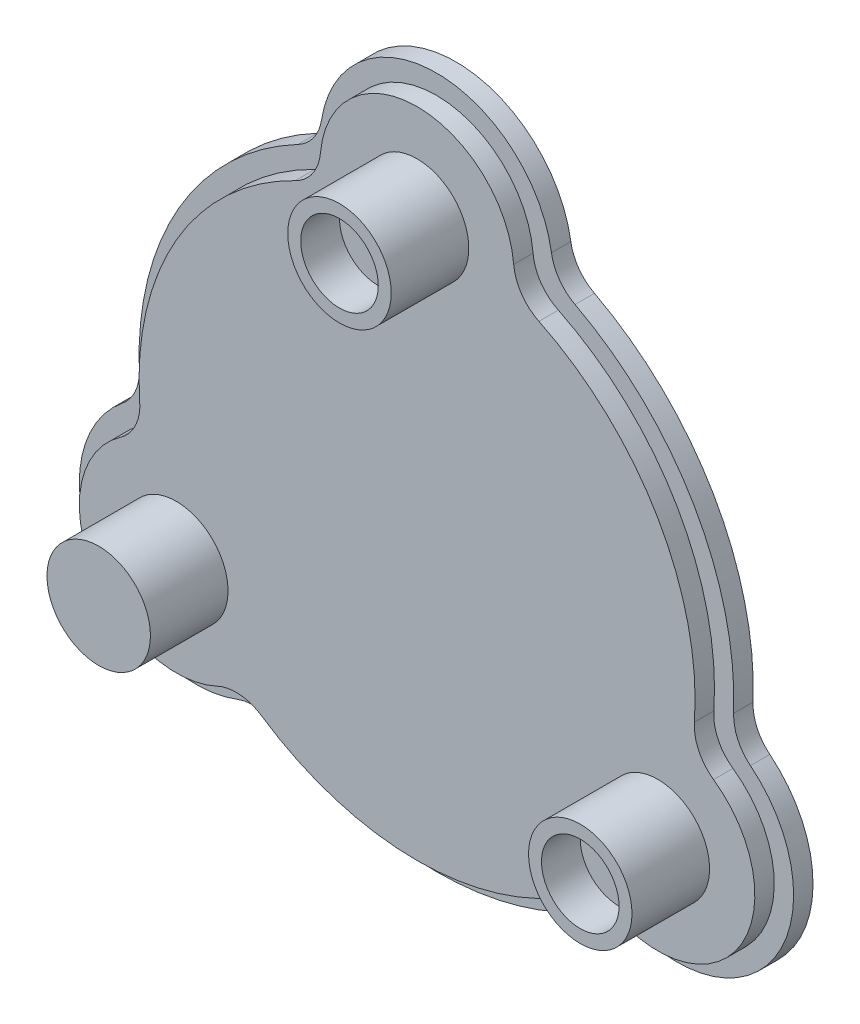
SolidWorks part; units mm, degrees
material "PE Low/Medium Density"
ref_plane "Front Plane" through (0, 0, 0) normal (0, 0, 1) x (1, 0, 0)
ref_plane "Top Plane" through (0, 0, 0) normal (0, 1, 0) x (1, 0, 0)
ref_plane "Right Plane" through (0, 0, 0) normal (1, 0, 0) x (0, 0, -1)
sketch "Sketch1" plane through (0, 0, 0) normal (0, 0, 1) x (1, 0, 0)
  arc A0 (-18846.1535, 38650) -> (-42894.9586, -3003.7523) centre (0, 0) ccw
  arc A1 (14941.4536, 44323.9958) -> (-14941.4536, 44323.9958) centre (0, 43000) ccw
  arc A2 (30914.9795, -35101.6763) -> (45856.4331, -9222.3195) centre (37239.0924, -21500) ccw
  arc A3 (-45856.4331, -9222.3195) -> (-30914.9795, -35101.6763) centre (-37239.0924, -21500) ccw
  circle A4 centre (0, 43000) radius 6000
  circle A5 centre (0, 43000) radius 3000
  circle A6 centre (37239.0924, -21500) radius 6000
  circle A7 centre (37239.0924, -21500) radius 3000
  circle A8 centre (-37239.0924, -21500) radius 6000
  circle A9 centre (-37239.0924, -21500) radius 3000
  arc A10 (-24048.8051, -35646.2477) -> (24048.8051, -35646.2477) centre (0, 0) ccw
  arc A11 (42894.9586, -3003.7523) -> (18846.1535, 38650) centre (0, 0) ccw
  arc A12 (30777.9137, -38300.392) -> (48558.0693, -7504.2592) centre (37239.0924, -21500) ccw
  arc A13 (45965.1907, -1789.2013) -> (21433.1016, 40701.6235) centre (0, 0) ccw
  arc A14 (17780.1556, 45804.6512) -> (-17780.1556, 45804.6512) centre (0, 43000) ccw
  arc A15 (-21433.1016, 40701.6235) -> (-45965.1907, -1789.2013) centre (0, 0) ccw
  arc A16 (-48558.0693, -7504.2592) -> (-30777.9137, -38300.392) centre (-37239.0924, -21500) ccw
  arc A17 (-24532.0892, -38912.4222) -> (24532.0892, -38912.4222) centre (0, 0) ccw
  circle A18 centre (0, 43000) radius 8000
  circle A19 centre (37239.0924, -21500) radius 8000
  circle A20 centre (-37239.0924, -21500) radius 8000
  arc A21 (14770.0739, 40383.7209) -> (-14770.0739, 40383.7209) centre (0, 43000) ccw construction
  arc A22 (-14770.0739, 40383.7209) -> (-42358.3652, -7400.6012) centre (0, 0) ccw construction
  arc A23 (-14941.4536, 44323.9958) -> (-18846.1535, 38650) centre (-21914.1319, 44941.8605) cw
  arc A24 (17987.7933, 42337.2093) -> (-17987.7933, 42337.2093) centre (0, 43000) ccw construction
  arc A25 (-17987.7933, 42337.2093) -> (-45658.9954, -5590.7187) centre (0, 0) ccw construction
  arc A26 (-17780.1556, 45804.6512) -> (-21433.1016, 40701.6235) centre (-24694.6605, 46895.3488) cw
  arc A27 (42358.3652, -7400.6012) -> (14770.0739, 40383.7209) centre (0, 0) ccw construction
  arc A28 (14941.4536, 44323.9958) -> (18846.1535, 38650) centre (21914.1319, 44941.8605) ccw
  arc A29 (45658.9954, -5590.7187) -> (17987.7933, 42337.2093) centre (0, 0) ccw construction
  arc A30 (21433.1016, 40701.6235) -> (17780.1556, 45804.6512) centre (24694.6605, 46895.3488) cw
  arc A31 (27588.2913, -32983.1197) -> (42358.3652, -7400.6012) centre (37239.0924, -21500) ccw construction
  arc A32 (42894.9586, -3003.7523) -> (45856.4331, -9222.3195) centre (49877.8588, -3492.7353) ccw
  arc A33 (27671.2021, -36746.4906) -> (45658.9954, -5590.7187) centre (37239.0924, -21500) ccw construction
  arc A34 (48558.0693, -7504.2592) -> (45965.1907, -1789.2013) centre (52959.8937, -2061.4711) cw
  arc A35 (-27588.2913, -32983.1197) -> (27588.2913, -32983.1197) centre (0, 0) ccw construction
  arc A36 (30914.9795, -35101.6763) -> (24048.8051, -35646.2477) centre (27963.7269, -41449.1252) ccw
  arc A37 (-27671.2021, -36746.4906) -> (27671.2021, -36746.4906) centre (0, 0) ccw construction
  arc A38 (30777.9137, -38300.392) -> (24532.0892, -38912.4222) centre (28265.2332, -44833.8778) ccw
  arc A39 (-45658.9954, -5590.7187) -> (-27671.2021, -36746.4906) centre (-37239.0924, -21500) ccw construction
  arc A40 (-30777.9137, -38300.392) -> (-24532.0892, -38912.4222) centre (-28265.2332, -44833.8778) cw
  arc A41 (-42358.3652, -7400.6012) -> (-27588.2913, -32983.1197) centre (-37239.0924, -21500) ccw construction
  arc A42 (-24048.8051, -35646.2477) -> (-30914.9795, -35101.6763) centre (-27963.7269, -41449.1252) ccw
  arc A43 (-42894.9586, -3003.7523) -> (-45856.4331, -9222.3195) centre (-49877.8588, -3492.7353) cw
  arc A44 (-45965.1907, -1789.2013) -> (-48558.0693, -7504.2592) centre (-52959.8937, -2061.4711) cw
  point P32 (0, 0)
  point P33 (0, 0)
  point P70 (0, 0)
  dimension "D1" = 3000
  dimension "D2" = 7000
  dimension "D3" = 7000
  dimension "D4" = 7000
  dimension "D5" = 7000
  dimension "D6" = 7000
  dimension "D7" = 7000
  dimension "D8" = 7000
  dimension "D9" = 7000
  dimension "D10" = 7000
  dimension "D11" = 7000
  dimension "D12" = 7000
extrude "Boss-Extrude5" add sketch "Sketch1" along normal blind 6000 and the other way blind 1 contours A0 A43 A3 A42 A10 A36 A2 A32 A11 A28 A1 A23
extrude "Boss-Extrude6" add sketch "Sketch1<7>" along normal blind 3000 contours A15 A44 A16 A40 A17 A38 A12 A34 A13 A30 A14 A26
sketch "Sketch1<7>" plane through (0, 0, 0) normal (0, 0, 1) x (1, 0, 0) same geometry as "Sketch1"
extrude "Boss-Extrude8" add sketch "Sketch1<10>" along normal blind 12000 contours A4 | A6 | A8
sketch "Sketch1<10>" plane through (0, 0, 0) normal (0, 0, 1) x (1, 0, 0) same geometry as "Sketch1"
extrude "Boss-Extrude9" add sketch "Sketch1<12>" along normal blind 18000 contours A20 A8 | A18 A4 | A19 A6 | A8 region at (-7773.7258, 43000, 0) region at (29465.3665, -21500, 0) region at (-45012.8182, -21500, 0)
sketch "Sketch1<12>" plane through (0, 0, 0) normal (0, 0, 1) x (1, 0, 0) same geometry as "Sketch1"
